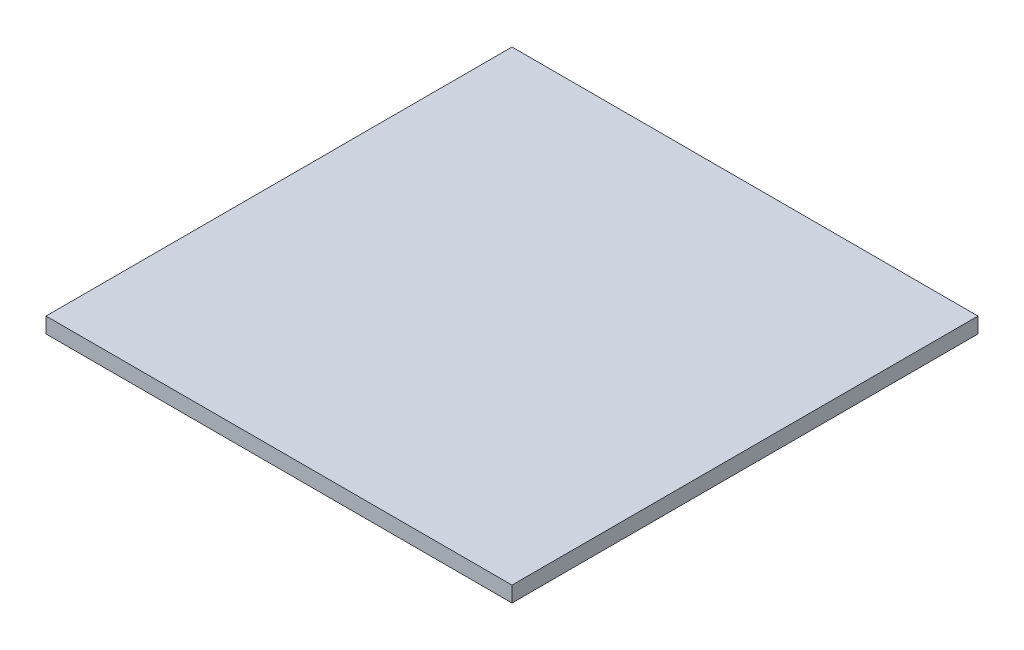
SolidWorks part; units mm, degrees
ref_plane "Front Plane" through (0, 0, 0) normal (0, 0, 1) x (1, 0, 0)
ref_plane "Top Plane" through (0, 0, 0) normal (0, 1, 0) x (1, 0, 0)
ref_plane "Right Plane" through (0, 0, 0) normal (1, 0, 0) x (0, 0, -1)
sketch "Sketch1" plane through (0, 0, 0) normal (0, 1, 0) x (1, 0, 0)
  line L1 (-24, -24) -> (24, -24)
  line L2 (-24, -24) -> (-24, 24)
  line L3 (-24, 24) -> (24, 24)
  line L4 (24, -24) -> (24, 24)
  line L5 (-24, -24) -> (24, 24) construction
  line L6 (-24, 24) -> (24, -24) construction
  point P0 (0, 0)
  dimension "D1" = 48
  dimension "D2" = 48
extrude "Boss-Extrude1" add sketch "Sketch1" along normal blind 1.6
